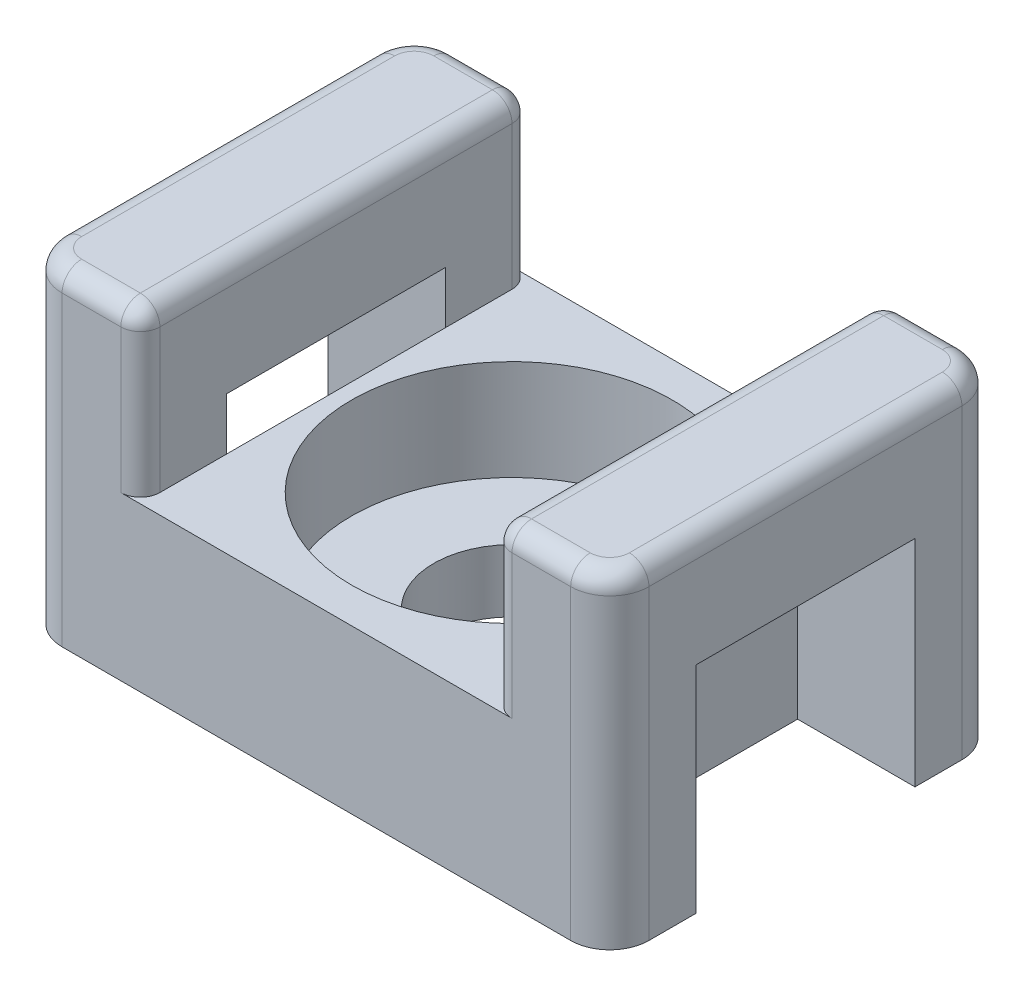
SolidWorks part; units mm, degrees
ref_plane "Front Plane" through (0, 0, 0) normal (0, 0, 1) x (1, 0, 0)
ref_plane "Top Plane" through (0, 0, 0) normal (0, 1, 0) x (1, 0, 0)
ref_plane "Right Plane" through (0, 0, 0) normal (1, 0, 0) x (0, 0, -1)
sketch "Sketch1" plane through (0, 0, 0) normal (0, 1, 0) x (1, 0, 0)
  line L1 (7.1438, -4.7625) -> (-7.1437, -4.7625)
  line L2 (7.1438, -4.7625) -> (7.1438, 4.7625)
  line L3 (7.1438, 4.7625) -> (-7.1437, 4.7625)
  line L4 (-7.1437, -4.7625) -> (-7.1437, 4.7625)
  line L5 (7.1438, -4.7625) -> (-7.1437, 4.7625) construction
  line L6 (7.1438, 4.7625) -> (-7.1437, -4.7625) construction
  circle A0 centre (0, 0) radius 1.905
  dimension "MT" = 3.81
  dimension "Length" = 14.2875
  dimension "Width" = 9.525
extrude "Boss-Extrude1" add sketch "Sketch1" along normal blind 7.9375
sketch "Sketch2" plane through (0, 0, 4.7625) normal (0, 0, 1) x (1, 0, 0)
  line L0 (-4.2862, 7.9375) -> (-4.2862, 3.9688)
  line L1 (-7.1437, 7.9375) -> (7.1438, 7.9375) construction
  line L2 (-4.2862, 3.9688) -> (4.2862, 3.9688)
  line L3 (4.2862, 3.9688) -> (4.2862, 7.9375)
  line L4 (0, 0) -> (0, 3.9688) construction
  line L5 (-7.1437, 0) -> (7.1438, 0) construction
  line L6 (4.2862, 3.9688) -> (7.1437, 3.9688) construction
  line L7 (7.1438, 7.9375) -> (7.1438, 0) construction
  line L8 (-4.2862, 7.9375) -> (4.2862, 7.9375)
  line L9 (-7.1437, 7.9375) -> (-7.1437, 0) construction
  dimension "D1" = 8.5725
  dimension "D2" = 2.8575
extrude "Cut-Extrude1" cut sketch "Sketch2" against normal through all
sketch "Sketch3" plane through (0, 0, 0) normal (1, 0, 0) x (0, 0, -1)
  line L0 (0, 0) -> (0, 3.9688) construction
  line L1 (-2.667, 5.2388) -> (2.667, 5.2388)
  line L2 (-2.667, 5.2388) -> (-2.667, 3.9688)
  line L3 (-2.667, 3.9688) -> (2.667, 3.9688)
  line L4 (2.667, 5.2388) -> (2.667, 3.9688)
  line L5 (-4.7625, 0) -> (4.7625, 0) construction
  line L6 (4.7625, 3.9688) -> (-4.7625, 3.9688) construction
  dimension "CH" = 1.27
  dimension "CW" = 5.334
extrude "Cut-Extrude2" cut sketch "Sketch3" against normal through all both and the other way through all
sketch "Sketch4" plane through (7.1438, 0, 0) normal (1, 0, 0) x (0, 0, -1)
  line L0 (-4.7625, 0) -> (4.7625, 0) construction
  line L1 (-2.667, 3.9688) -> (2.667, 3.9688)
  line L2 (-2.667, 3.9688) -> (-2.667, 0)
  line L3 (-2.667, 0) -> (2.667, 0)
  line L4 (2.667, 3.9688) -> (2.667, 0)
  line L5 (2.667, 3.9688) -> (2.667, 5.2388) construction
extrude "Cut-Extrude3" cut sketch "Sketch4" against normal up to vertex (2.8575 mm away) up to point (4.2862, 7.9375, -4.7625)
sketch "Sketch5" plane through (-7.1437, 0, 0) normal (-1, 0, 0) x (0, 0, 1)
  line L4 (2.667, 3.9688) -> (-2.667, 3.9688)
  line L5 (-2.667, 3.9688) -> (-2.667, 0)
  line L6 (-2.667, 0) -> (2.667, 0)
  line L7 (2.667, 0) -> (2.667, 3.9688)
  line L8 (2.667, 3.9688) -> (-2.667, 3.9688)
  line L9 (-2.667, 3.9688) -> (-2.667, 0)
  line L10 (-2.667, 0) -> (2.667, 0)
  line L11 (2.667, 0) -> (2.667, 3.9688)
  dimension "D1" = 0
extrude "Cut-Extrude4" cut sketch "Sketch5" against normal up to vertex (2.8575 mm away) up to point (-4.2862, 7.9375, -4.7625)
sketch "Sketch6" plane through (0, 3.9688, 0) normal (0, 1, 0) x (1, 0, 0)
  line L10 (3.9053, 2.667) -> (3.9053, -2.667)
  line L11 (3.9053, 2.667) -> (3.9053, -2.667) construction
  circle A0 centre (0, 0) radius 3.9053
  dimension "D1" = 0.381
extrude "Cut-Extrude5" cut sketch "Sketch6" against normal offset from surface (2.4448 mm away) 1.524 up to face at (0, 0, 0)
fillet "Fillet2" radius 0.9525 4 edges at (-7.1437, 3.9688, -4.7625) (-7.1437, 3.9688, 4.7625) (7.1438, 3.9688, -4.7625) (7.1438, 3.9688, 4.7625)
fillet "Fillet3" radius 0.4762 16 edges at (-4.2862, 7.9375, 0) (-5.2387, 7.9375, 4.7625) (-6.8648, 7.9375, 4.4835) (-7.1437, 7.9375, 0) (-6.8648, 7.9375, -4.4835) (-5.2387, 7.9375, -4.7625) (6.8648, 7.9375, 4.4835) (5.2388, 7.9375, 4.7625) (4.2862, 7.9375, 0) (5.2388, 7.9375, -4.7625) (6.8648, 7.9375, -4.4835) (7.1438, 7.9375, 0) (4.2862, 5.9531, -4.7625) (4.2862, 5.9531, 4.7625) (-4.2862, 5.9531, -4.7625) (-4.2862, 5.9531, 4.7625)
equation "\"D1@Sketch2\"=\"Length@Sketch1\"*.6"
equation "\"D1@Fillet2\"=\"D2@Sketch2\"/3"
equation "\"D1@Fillet3\"=\"D1@Fillet2\"/2"
